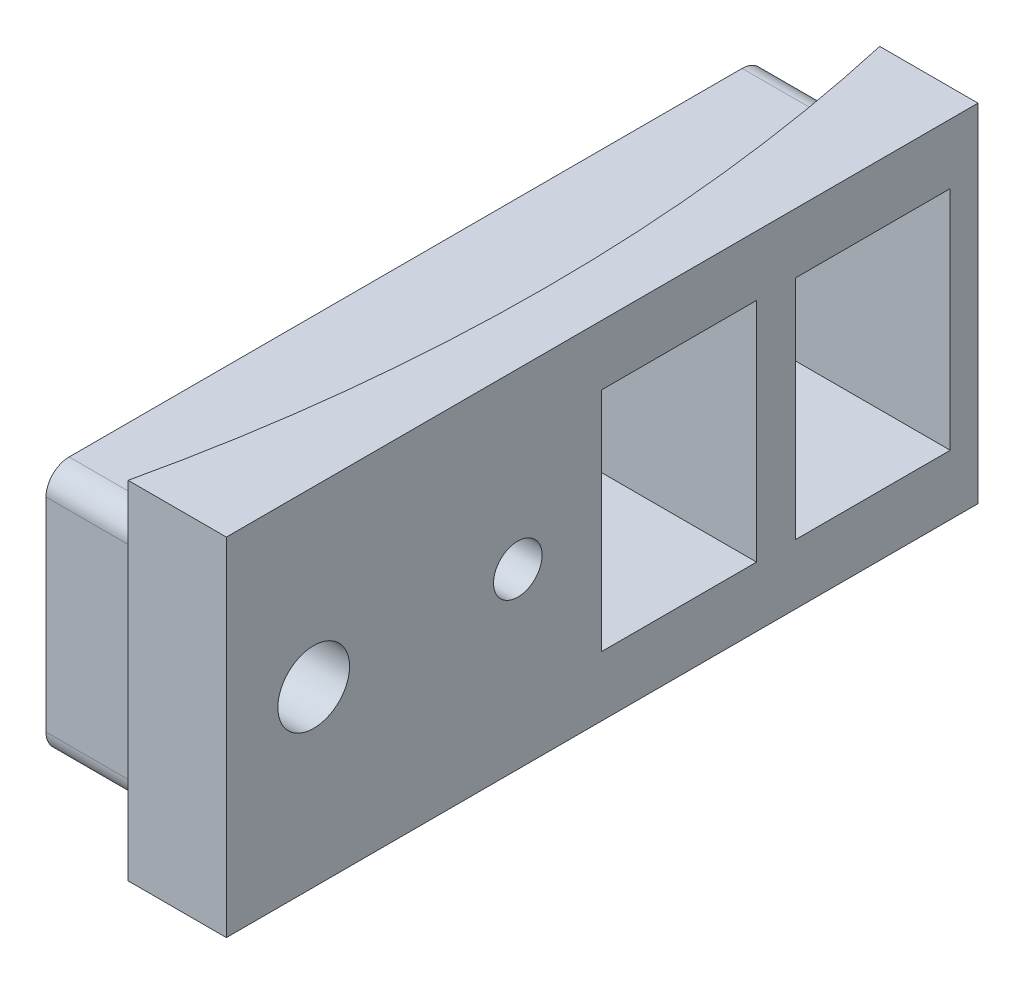
SolidWorks part; units mm, degrees
ref_plane "Front Plane" through (0, 0, 0) normal (0, 0, 1) x (1, 0, 0)
ref_plane "Top Plane" through (0, 0, 0) normal (0, 1, 0) x (1, 0, 0)
ref_plane "Right Plane" through (0, 0, 0) normal (1, 0, 0) x (0, 0, -1)
sketch "Sketch1" plane through (0, 0, 0) normal (0, 1, 0) x (1, 0, 0)
  line L0 (143.7878, 32.5) -> (152.2878, 32.5)
  line L1 (152.2878, -32.5) -> (152.2878, 32.5)
  line L2 (152.2878, -32.5) -> (143.7878, -32.5)
  line L3 (0, 0) -> (147.415, 0) construction
  circle A0 centre (0, 0) radius 147.415
  dimension "D1" = 294.83
  dimension "D2" = 65
  dimension "D3" = 8.5
extrude "Boss-Extrude1" add sketch "Sketch1" along normal blind 30 contours A0 L2 L1 L0 region at (149.154, 0, 0)
sketch "Sketch2" plane through (152.2878, 0, 0) normal (1, 0, 0) x (0, 0, -1)
  line L0 (-32.5, 15) -> (32.5, 15) construction
  line L1 (-32.5, 30) -> (-32.5, 0) construction
  line L2 (32.5, 30) -> (32.5, 0) construction
  line L3 (-31.1, 25.8) -> (31.1, 25.8)
  line L5 (-24.95, 9.5) -> (-24.95, 20.5) construction
  line L6 (16.7, 24.8) -> (30.1, 24.8)
  line L7 (16.7, 24.8) -> (16.7, 5.2)
  line L8 (16.7, 5.2) -> (30.1, 5.2)
  line L9 (30.1, 24.8) -> (30.1, 5.2)
  line L10 (-0.05, 24.8) -> (13.35, 24.8)
  line L11 (-0.05, 24.8) -> (-0.05, 5.2)
  line L12 (-0.05, 5.2) -> (13.35, 5.2)
  line L13 (13.35, 24.8) -> (13.35, 5.2)
  line L14 (-30.1, 9.5) -> (-19.8, 9.5)
  line L15 (-30.1, 9.5) -> (-30.1, 20.5)
  line L16 (-30.1, 20.5) -> (-19.8, 20.5)
  line L17 (-19.8, 9.5) -> (-19.8, 20.5)
  line L18 (-7.3, 18.75) -> (-7.3, 11.25) construction
  line L19 (-11.05, 18.75) -> (-3.55, 18.75)
  line L20 (-11.05, 18.75) -> (-11.05, 11.25)
  line L21 (-11.05, 11.25) -> (-3.55, 11.25)
  line L22 (-3.55, 18.75) -> (-3.55, 11.25)
  line L25 (30.1, 24.8) -> (30.1, 5.2)
  line L26 (31.1, 25.8) -> (31.1, 4.2)
  line L27 (-31.1, 4.2) -> (31.1, 4.2)
  line L28 (-31.1, 25.8) -> (-31.1, 4.2)
  line L29 (0, 0) -> (0, 30) construction
  line L30 (-32.5, 30) -> (32.5, 30) construction
  line L31 (-30.1, 24.8) -> (-30.1, 5.2) construction
  line L32 (-30.1, 24.8) -> (30.1, 24.8) construction
  line L33 (-30.1, 5.2) -> (30.1, 5.2) construction
  circle A0 centre (-7.3, 15) radius 2.1
  circle A1 centre (-24.95, 15) radius 3.1
  circle A2 centre (-24.95, 15) radius 2.5
  circle A4 centre (-24.95, 15) radius 10 construction
  circle A5 centre (-7.3, 15) radius 1.8
  dimension "D5" = 6.2
  dimension "D6" = 5
  dimension "D7" = 4.2
  dimension "D8" = 20
  dimension "D9" = 3.6
  dimension "D1" = 19.6
  dimension "D2" = 13.4
  dimension "D3" = 3.35
  dimension "D4" = 62.2
  dimension "D10" = 11
  dimension "D11" = 10.3
  dimension "D12" = 7.5
  dimension "D13" = 1.4
  dimension "D14" = 1
  dimension "D16" = 3.5
  dimension "D15" = 1
extrude "Boss-Extrude2" add sketch "Sketch2" against normal blind 17 contours L3 L28 L27 L26 L9 L8 L12 | L11 L19 L22 L21 L20 L17 L14 L15 L16 | A1 A2 | A2 | L22 L19 L20 L21 A0 | A0 A5 | A5 | L13 L11 L12 | L13 L7 | L9 L7 L8 | L14 L17 L16 L15 A1 region at (152.2878, 25.1416, 0) region at (152.2878, 15, -23.4) region at (152.2878, 15, -6.65) region at (152.2878, 15, 29.9493) region at (152.2878, 18.6439, 7.3) region at (152.2878, 15, 9.3406) region at (152.2878, 15, 27.9623) region at (152.2878, 15, 24.95) region at (152.2878, 15, 7.3)
extrude "Cut-Extrude3" cut sketch "Sketch2<6>" against normal up to surface (17 mm away) contours L13 L11 L12 | L9 L7 L8 | A2 | A1 A2 | A5 | A0 A5 region at (152.2878, 15, -23.4) region at (152.2878, 15, -6.65) region at (152.2878, 15, 9.3406) region at (152.2878, 15, 27.9623) region at (152.2878, 15, 24.95) region at (152.2878, 15, 7.3) up to face at (135.2878, 15, 0)
sketch "Sketch2<6>" plane through (152.2878, 0, 0) normal (1, 0, 0) x (0, 0, -1) same geometry as "Sketch2"
extrude "Cut-Extrude5" cut sketch "Sketch2<8>" against normal up to surface (17 mm away) from offset 7 contours L22 L19 L20 L21 A0 | L14 L17 L16 L15 A1 region at (152.2878, 15, 29.9493) region at (152.2878, 18.6439, 7.3) up to face at (135.2878, 15, -6.65) offset against normal yes
sketch "Sketch2<8>" plane through (152.2878, 0, 0) normal (1, 0, 0) x (0, 0, -1) same geometry as "Sketch2"
fillet "Fillet1" radius 2 4 edges at (139.6924, 4.2, 31.1) (139.6924, 25.8, 31.1) (139.6924, 4.2, -31.1) (139.6924, 25.8, -31.1)
